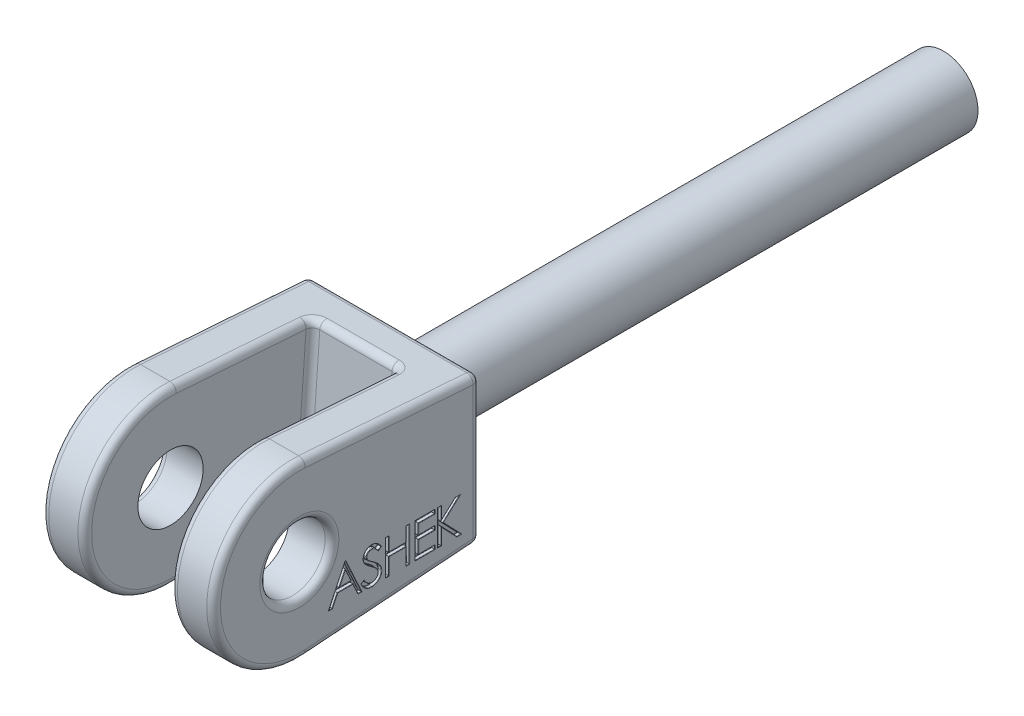
SolidWorks part; units mm, degrees
ref_plane "Front Plane" through (0, 0, 0) normal (0, 0, 1) x (1, 0, 0)
ref_plane "Top Plane" through (0, 0, 0) normal (0, 1, 0) x (1, 0, 0)
ref_plane "Right Plane" through (0, 0, 0) normal (1, 0, 0) x (0, 0, -1)
sketch "Sketch1" plane through (0, 0, 0) normal (0, 0, 1) x (1, 0, 0)
  circle A0 centre (0, 0) radius 1
  dimension "D1" = 2
extrude "Boss-Extrude1" add sketch "Sketch1" against normal blind 16
sketch "Sketch2" plane through (0, 0, 0) normal (1, 0, 0) x (0, 0, -1)
  line L0 (0, -2.125) -> (0, 2.125)
  line L2 (0, 0) -> (-5.2536, 0) construction
  line L3 (-5.0745, 2.49) -> (0, 2.125)
  line L4 (0, -2.125) -> (-5.0745, -2.49)
  circle A0 centre (-5.2536, 0) radius 0.95
  arc A1 (-5.0745, 2.49) -> (-5.0745, -2.49) centre (-5.2536, 0) ccw
  point P6 (0, 0)
  point P11 (-7.75, 0)
  dimension "D2" = 1.9
  dimension "D3" = 7.75
  dimension "D1" = 4.25
  dimension "D4" = 4.98
extrude "Boss-Extrude2" add sketch "Sketch2" along normal mid plane 5
sketch "Sketch3" plane through (0, 2.1141, -0.1521) normal (0, 0.9974, -0.0717) x (1, 0, 0)
  line L0 (2.5, -5.24) -> (-2.5, -5.24) construction
  line L1 (-1.25, -9.2301) -> (1.25, -9.2301)
  line L2 (-1.25, -9.2301) -> (-1.25, -1.25)
  line L3 (-1.25, -1.25) -> (1.25, -1.25)
  line L4 (1.25, -9.2301) -> (1.25, -1.25)
  line L5 (-1.25, -9.2301) -> (1.25, -1.25) construction
  line L6 (-1.25, -1.25) -> (1.25, -9.2301) construction
  point P0 (0, -5.24)
  dimension "D1" = 1.25
  dimension "D2" = 1.25
extrude "Cut-Extrude1" cut sketch "Sketch3" against normal blind 9
fillet "Fillet1" radius 0.2 22 edges at (-1.25, 0, 7.75) (1.25, 0, 7.75) (0, -2.125, 0) (-1.25, -2.3583, 3.2439) (1.25, -2.3583, 3.2439) (-1.25, 2.3469, 3.0846) (0, 2.125, 0) (1.25, 2.3469, 3.0846) (-2.5, 0, 4.3036) (-2.5, 0, 7.75) (-2.5, -2.3075, 2.5372) (-2.5, 0, 0) (-2.5, 2.3075, 2.5372) (2.5, 0, 4.3036) (2.5, 0, 0) (2.5, -2.3075, 2.5372) (2.5, 0, 7.75) (2.5, 2.3075, 2.5372) (0, -2.2267, 1.4134) (-1.25, -0.0115, 1.2541) (0, 2.2037, 1.0947) (1.25, -0.0115, 1.2541)
fillet "Fillet2" radius 0.2 1 edges at (1, 0, 0)
sketch "Sketch4" plane through (2.5, 0, 0) normal (1, 0, 0) x (0, 0, -1)
  text T0 "ASHEK" font "Century Gothic" height 1
extrude "Cut-Extrude2" cut sketch "Sketch4" against normal blind 0.1
fillet "Fillet3" radius 0.01 127 edges at (2.4, -1.1519, 3.6753) (2.4, -1.6519, 3.4933) (2.4, -1.4916, 3.616) (2.4, -1.3313, 3.9165) (2.4, -1.4916, 4.2192) (2.4, -1.6519, 4.3442) (2.4, -1.1519, 4.156) (2.4, -0.6519, 3.9124) (2.4, -1.0378, 3.8253) (2.4, -1.0378, 4.004) (2.4, -1.2288, 3.9158) (2.45, -1.3313, 3.6899) (2.5, -0.8262, 2.9158) (2.5, -1.4336, 3.4099) (2.5, -1.4083, 2.6522) (2.5, -1.1647, 2.3958) (2.5, -1.4083, 2.1394) (2.5, -1.6519, 2.0945) (2.5, -1.1519, 2.0496) (2.5, -0.6519, 2.0945) (2.5, -0.857, 2.1394) (2.5, -1.0621, 2.3958) (2.5, -0.857, 2.6522) (2.5, -0.6519, 2.6971) (2.5, -1.1519, 2.7419) (2.5, -1.6519, 2.6971) (2.5, -1.6006, 1.3137) (2.5, -1.5493, 1.5509) (2.5, -1.357, 1.7881) (2.5, -1.1647, 1.5509) (2.5, -1.1134, 1.3137) (2.5, -1.0621, 1.5509) (2.5, -0.9083, 1.7881) (2.5, -0.7544, 1.5509) (2.5, -0.7031, 1.3137) (2.5, -0.6519, 1.5958) (2.5, -1.1519, 1.8778) (2.5, -1.6519, 1.5958) (2.5, -1.4106, 1.1291) (2.5, -1.4106, 0.8972) (2.5, -1.6519, 0.6056) (2.5, -1.3762, 0.8107) (2.5, -0.8762, 0.8299) (2.5, -0.6519, 0.6482) (2.5, -0.8423, 0.9207) (2.5, -0.8423, 1.1291) (2.5, -0.6519, 1.174) (2.5, -1.1519, 1.2189) (2.5, -1.6519, 1.174) (2.5, -1.6519, 4.3442) (2.5, -1.4916, 4.2192) (2.5, -1.3313, 3.9165) (2.5, -1.4916, 3.616) (2.5, -1.6519, 3.4933) (2.5, -1.1519, 3.6753) (2.5, -0.6519, 3.9124) (2.5, -1.1519, 4.156) (2.5, -1.0378, 4.004) (2.5, -1.0378, 3.8253) (2.5, -1.2288, 3.9158) (2.4, -0.6519, 1.174) (2.4, -0.8423, 1.1291) (2.4, -0.8423, 0.9207) (2.4, -0.6519, 0.6482) (2.4, -0.8762, 0.8299) (2.4, -1.3762, 0.8107) (2.4, -1.6519, 0.6056) (2.4, -1.4106, 0.8972) (2.4, -1.4106, 1.1291) (2.4, -1.6519, 1.174) (2.4, -1.1519, 1.2189) (2.4, -0.6519, 1.5958) (2.4, -0.7031, 1.3137) (2.4, -0.7544, 1.5509) (2.4, -0.9083, 1.7881) (2.4, -1.0621, 1.5509) (2.4, -1.1134, 1.3137) (2.4, -1.1647, 1.5509) (2.4, -1.357, 1.7881) (2.4, -1.5493, 1.5509) (2.4, -1.6006, 1.3137) (2.4, -1.6519, 1.5958) (2.4, -1.1519, 1.8778) (2.4, -0.6519, 2.6971) (2.4, -0.857, 2.6522) (2.4, -1.0621, 2.3958) (2.4, -0.857, 2.1394) (2.4, -0.6519, 2.0945) (2.4, -1.1519, 2.0496) (2.4, -1.6519, 2.0945) (2.4, -1.4083, 2.1394) (2.4, -1.1647, 2.3958) (2.4, -1.4083, 2.6522) (2.4, -1.6519, 2.6971) (2.4, -1.1519, 2.7419) (2.4, -1.4336, 3.4099) (2.4, -0.8262, 2.9158)
